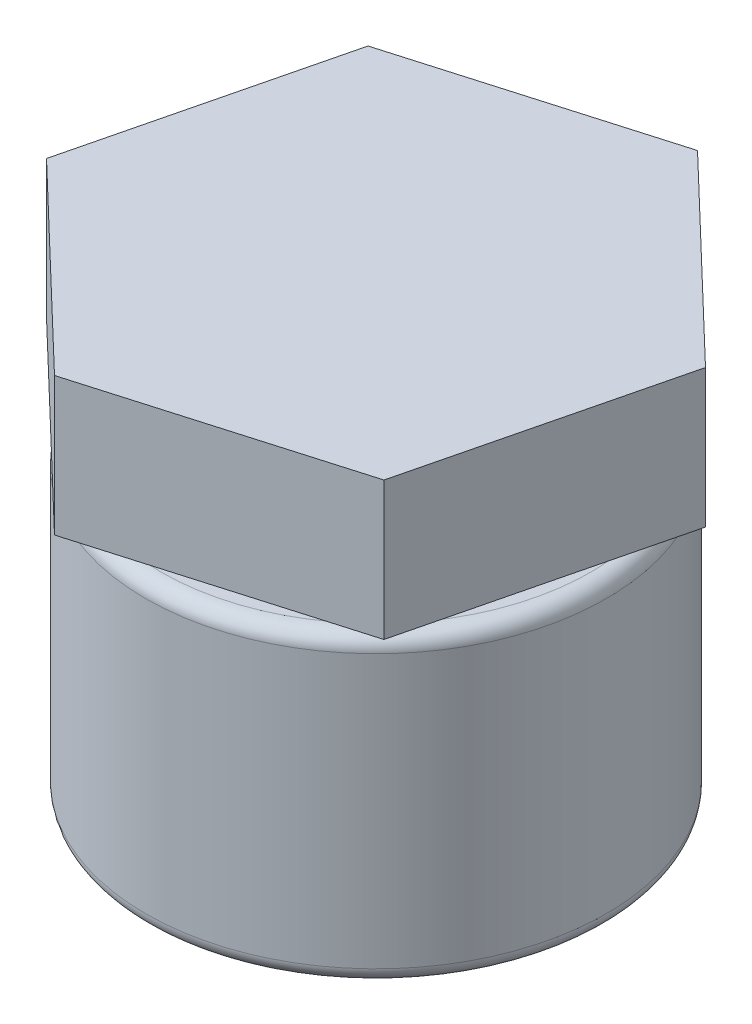
SolidWorks part; units mm, degrees
ref_plane "Спереди" through (0, 0, 0) normal (0, 0, 1) x (1, 0, 0)
ref_plane "Сверху" through (0, 0, 0) normal (0, 1, 0) x (1, 0, 0)
ref_plane "Справа" through (0, 0, 0) normal (1, 0, 0) x (0, 0, -1)
sketch "Эскиз1" plane through (0, 0, 0) normal (0, 0, 1) x (1, 0, 0)
  line L0 (0, 66.5427) -> (17.1817, 66.5427)
  line L1 (17.1817, 66.5427) -> (17.1817, 47.4496)
  line L2 (17.1817, 47.4496) -> (28.2479, 47.4496)
  line L3 (28.2479, 47.4496) -> (28.2479, 9.3272)
  line L4 (28.2479, 9.3272) -> (30.1009, 9.3272)
  line L5 (30.1009, 9.3272) -> (30.1009, 7.1348)
  line L6 (30.1009, 7.1348) -> (28.2479, 7.1348)
  line L7 (28.2479, 7.1348) -> (28.2479, -5.0963)
  line L8 (28.2479, -5.0963) -> (149.9758, -5.0963)
  line L9 (149.9758, -5.0963) -> (149.9758, -202.86)
  line L10 (149.9758, -202.86) -> (0, -202.86)
  line L11 (0, -202.86) -> (0, -186.0078)
  line L12 (0, -186.0078) -> (141.1521, -186.0078)
  line L13 (141.1521, -186.0078) -> (141.1521, -11.3202)
  line L14 (141.1521, -11.3202) -> (0, -11.3202)
  line L15 (0, -11.3202) -> (0, 66.5427)
  point P17 (0, -202.86)
  point P18 (0, 0)
  point P19 (0, -186.0078)
revolve "Повернуть1" add sketch "Эскиз1" angle 360 about L15
fillet "Скругление1" radius 10 1 edges at (0, -5.0963, -149.9758)
fillet "Скругление2" radius 10 1 edges at (0, -202.86, -149.9758)
sketch "Эскиз2" plane through (0, 9.3272, 0) normal (0, 1, 0) x (1, 0, 0)
  line L1 (-125.0225, 119.832) -> (-166.2888, -48.3566)
  line L2 (-166.2888, -48.3566) -> (-41.2663, -168.1887)
  line L3 (-41.2663, -168.1887) -> (125.0225, -119.832)
  line L4 (125.0225, -119.832) -> (166.2888, 48.3566)
  line L5 (166.2888, 48.3566) -> (41.2663, 168.1887)
  line L6 (41.2663, 168.1887) -> (-125.0225, 119.832)
  circle A0 centre (0, 0) radius 149.9758 construction
  circle A1 centre (0, 0) radius 149.9758 construction
extrude "Бобышка-Вытянуть1" add sketch "Эскиз2" along normal blind 90 separate body
revolve "Вырез-Повернуть1" cut sketch "Эскиз1<3>" angle 360 about L15
sketch "Эскиз1<3>" plane through (0, 0, 0) normal (0, 0, 1) x (1, 0, 0) same geometry as "Эскиз1"
